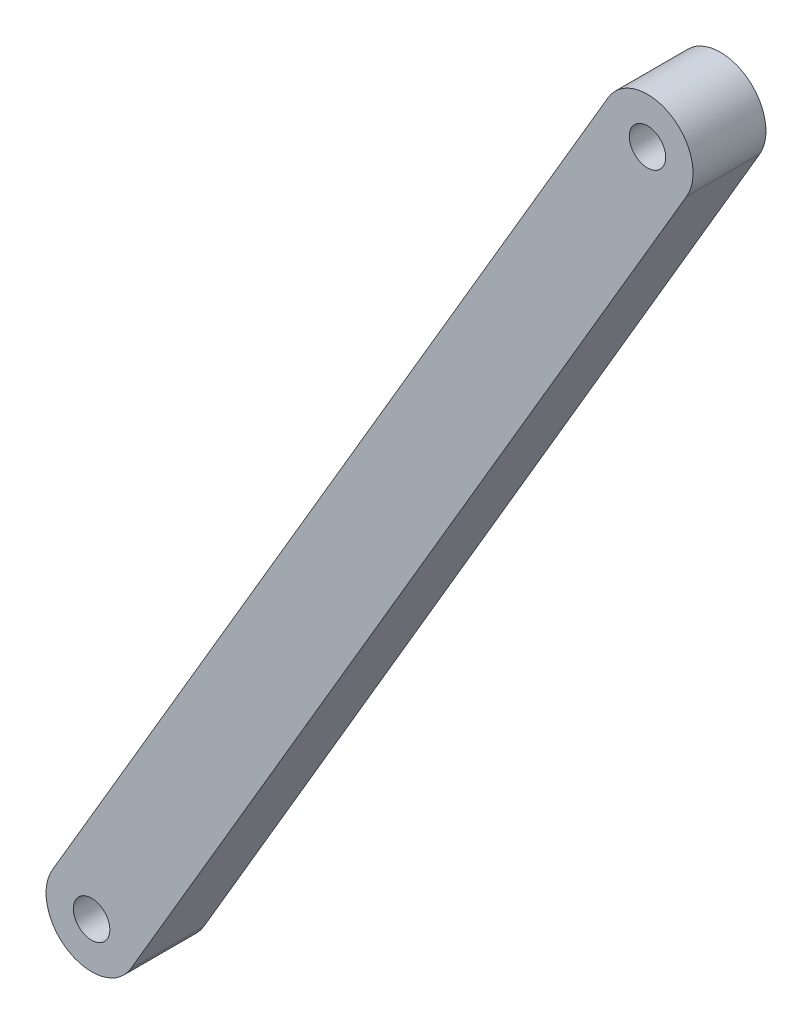
SolidWorks part; units mm, degrees
ref_plane "Ebene vorne" through (0, 0, 0) normal (0, 0, 1) x (1, 0, 0)
ref_plane "Ebene oben" through (0, 0, 0) normal (0, 1, 0) x (1, 0, 0)
ref_plane "Ebene rechts" through (0, 0, 0) normal (1, 0, 0) x (0, 0, -1)
sketch "Skizze1" plane through (0, 0, 0) normal (0, 0, 1) x (1, 0, 0)
  line L1 (-11.6, 468.1) -> (34, 468.1)
  line L2 (-11.6, 468.1) -> (-11.6, 444.1)
  line L3 (-11.6, 444.1) -> (34, 444.1)
  line L4 (34, 468.1) -> (34, 444.1)
  circle A0 centre (29, 456.1) radius 2
  point P6 (-11.6, 456.1)
sketch "Skizze2" plane through (0, 0, 0) normal (0, 0, 1) x (1, 0, 0)
  circle A0 centre (0, 560) radius 4
  circle A1 centre (90, 560) radius 4
sketch "Skizze3" plane through (0, 0, 0) normal (0, 0, 1) x (1, 0, 0)
  line L0 (24.6882, 458.6315) -> (85.6882, 562.5315)
  line L1 (33.3118, 453.5685) -> (94.3118, 557.4685)
  circle A0 centre (90, 560) radius 2
  circle A1 centre (29, 456.1) radius 2
  arc A2 (24.6882, 458.6315) -> (33.3118, 453.5685) centre (29, 456.1) ccw
  arc A3 (94.3118, 557.4685) -> (85.6882, 562.5315) centre (90, 560) ccw
extrude "Aufsatz-Linear austragen1" add sketch "Skizze3" along normal blind 4 and the other way blind 4
